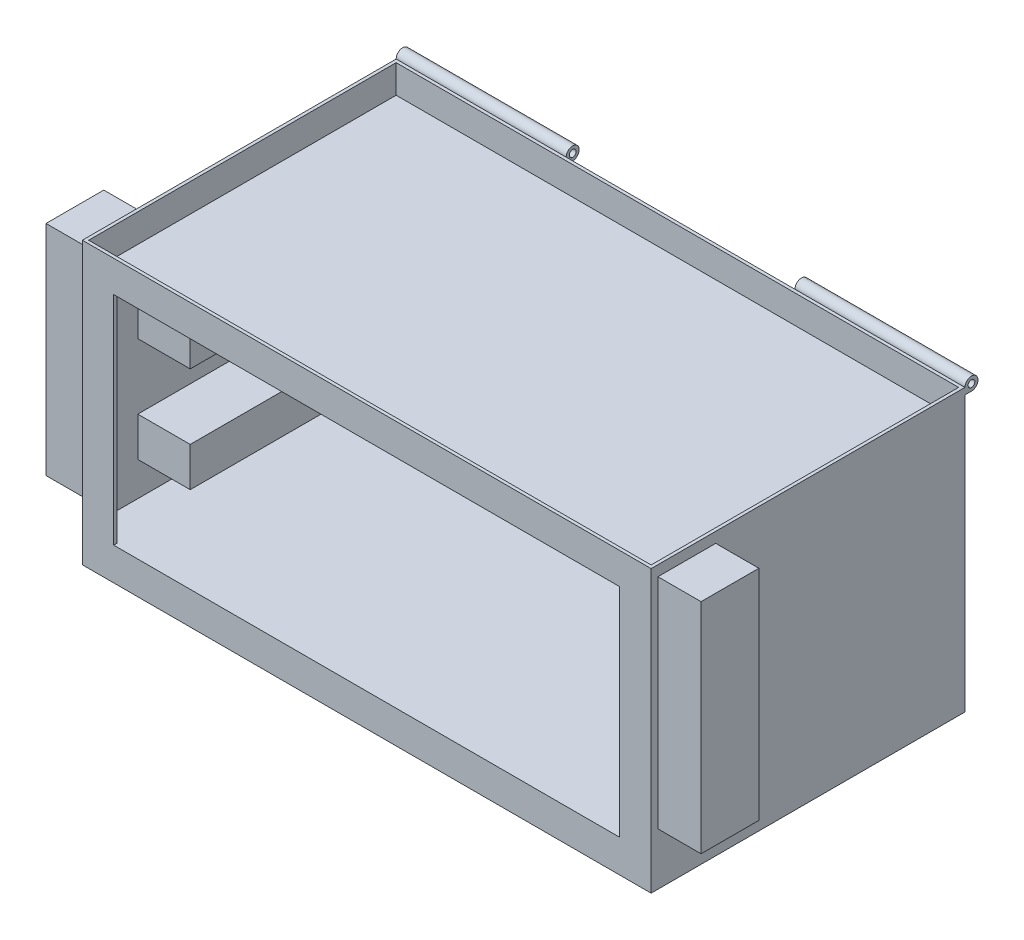
SolidWorks part; units mm, degrees
note: The reader was unsure of these and kept them because the rebuilt part matched: shared geometry of "Sketch1<13>", "Sketch1<14>", "Sketch1<15>".
material "AISI 4130 Steel, normalized at 870C"
ref_plane "Front Plane" through (0, 0, 0) normal (0, 0, 1) x (1, 0, 0)
ref_plane "Top Plane" through (0, 0, 0) normal (0, 1, 0) x (1, 0, 0)
ref_plane "Right Plane" through (0, 0, 0) normal (1, 0, 0) x (0, 0, -1)
sketch "Sketch1" plane through (0, 0, 0) normal (0, 1, 0) x (1, 0, 0)
  line L0 (0, 0) -> (-1.524, 0) construction
  line L9 (0, 0) -> (273.177, 0)
  line L10 (0, 0) -> (0, 149.352)
  line L11 (0, 149.352) -> (273.177, 149.352)
  line L12 (273.177, 0) -> (273.177, 149.352)
  line L13 (-1.524, -1.524) -> (274.701, -1.524)
  line L14 (-1.524, -1.524) -> (-1.524, 150.876)
  line L15 (-1.524, 150.876) -> (274.701, 150.876)
  line L16 (274.701, -1.524) -> (274.701, 150.876)
  line L17 (0, 149.352) -> (0, 150.876) construction
  line L18 (273.177, 149.352) -> (274.701, 149.352) construction
  line L19 (273.177, 0) -> (273.177, -1.524) construction
  line L20 (13.716, 0) -> (13.716, -1.524)
  line L21 (136.5885, 150.876) -> (136.5885, -1.524) construction
  line L22 (259.461, 0) -> (259.461, -1.524)
  dimension "D1" = 1.524
  dimension "D2" = 276.225
  dimension "D3" = 152.4
  dimension "D4" = 15.24
extrude "Bulk-Extrude" add sketch "Sketch1" against normal blind 136.525 contours L14 L13 L16 L15
extrude "Inner Shell-Cut" cut sketch "Sketch1<13>" against normal offset from surface (120.65 mm away) 15.875 contours L9 L12 L11 L10 | L22 L9 L20 L13 up to face at (136.5885, -136.525, -74.676)
sketch "Sketch1<13>" plane through (0, 0, 0) normal (0, 1, 0) x (1, 0, 0) same geometry as "Sketch1"
extrude "Top Wall-Extrude" add sketch "Sketch1<14>" against normal blind 15.24 contours L22 L9 L20 L13
sketch "Sketch1<14>" plane through (0, 0, 0) normal (0, 1, 0) x (1, 0, 0) same geometry as "Sketch1"
extrude "Top Floor-Extrude" add sketch "Sketch1<15>" along normal blind 1.524 from surface at -15.24 contours L9 L12 L11 L10 starting at face at (136.5885, -15.24, 0.762)
sketch "Sketch1<15>" plane through (0, 0, 0) normal (0, 1, 0) x (1, 0, 0) same geometry as "Sketch1"
ref_plane "Mid Plane" through (136.5885, 0, 0) normal (1, 0, 0) x (0, 0, -1)
sketch "Sketch5" plane through (274.701, 0, 0) normal (1, 0, 0) x (0, 0, -1)
  line L0 (150.876, 0) -> (154.051, 0)
  line L2 (154.051, -3.175) -> (150.876, -3.175)
  line L3 (150.876, -136.525) -> (150.876, 0) construction
  circle A0 centre (154.051, 0) radius 3.175
  circle A1 centre (154.051, 0) radius 1.651
  dimension "D1" = 1.524
  dimension "D2" = 6.35
extrude "Hinge-Extrude" add sketch "Sketch5" against normal blind 82.55
mirror "Mirror1" about plane through (136.5885, 0, 0) normal (1, 0, 0) of "Hinge-Extrude"
sketch "Sketch7" plane through (0, 0, -149.352) normal (0, 0, 1) x (1, 0, 0)
  line L0 (273.177, -120.65) -> (273.177, -15.24) construction
  line L1 (0, -34.29) -> (25.4635, -34.29)
  line L2 (0, -34.29) -> (0, -53.34)
  line L3 (0, -53.34) -> (25.4635, -53.34)
  line L4 (25.4635, -34.29) -> (25.4635, -53.34)
  line L5 (273.177, -34.29) -> (247.7135, -34.29)
  line L6 (273.177, -34.29) -> (273.177, -53.34)
  line L7 (273.177, -53.34) -> (247.7135, -53.34)
  line L8 (247.7135, -34.29) -> (247.7135, -53.34)
  line L9 (0, -120.65) -> (0, -15.24) construction
  line L10 (0, -85.09) -> (25.4635, -85.09)
  line L11 (0, -85.09) -> (0, -104.14)
  line L12 (0, -104.14) -> (25.4635, -104.14)
  line L13 (25.4635, -85.09) -> (25.4635, -104.14)
  line L14 (0, -15.24) -> (0, -34.29) construction
  line L15 (273.177, -85.09) -> (247.7135, -85.09)
  line L16 (273.177, -85.09) -> (273.177, -104.14)
  line L17 (273.177, -104.14) -> (247.7135, -104.14)
  line L18 (247.7135, -85.09) -> (247.7135, -104.14)
  line L19 (0, -15.24) -> (273.177, -15.24) construction
  line L20 (273.177, -15.24) -> (273.177, -34.29) construction
  line L21 (0, -53.34) -> (0, -85.09) construction
  line L22 (273.177, -53.34) -> (273.177, -85.09) construction
  dimension "D1" = 19.05
  dimension "D2" = 31.75
  dimension "D3" = 19.05
  dimension "D4" = 222.25
extrude "Rails-Extrude" add sketch "Sketch7" along normal offset from surface (125.476 mm away) 25.4 up to face at (136.5885, -68.2625, 1.524)
sketch "Sketch8" [suppressed] plane through (274.701, 0, 0) normal (1, 0, 0) x (0, 0, -1)
  line L0 (-1.524, -129.2098) -> (150.876, -129.2098) construction
  line L1 (-1.524, -136.525) -> (-1.524, 0) construction
  line L2 (150.876, -136.525) -> (150.876, -3.175) construction
  line L3 (-1.524, -136.525) -> (150.876, -136.525) construction
  line L4 (-1.524, -121.8946) -> (150.876, -121.8946) construction
  line L5 (-1.524, -135.89) -> (150.876, -135.89) construction
  line L6 (-0.889, -121.8946) -> (-0.889, -136.525) construction
  line L7 (150.241, -121.8946) -> (150.241, -136.525) construction
  line L8 (74.676, -135.89) -> (74.676, 0) construction
  line L9 (-1.524, 0) -> (150.876, 0) construction
  circle A0 centre (11.176, -129.2098) radius 4.7625
  circle A1 centre (138.176, -129.2098) radius 4.7625
  dimension "D6" = 9.525
  dimension "D7" = 12.7
  dimension "D1" = 7.3152
  dimension "D2" = 14.6304
  dimension "D3" = 0.635
  dimension "D4" = 0.635
  dimension "D5" = 0.635
sketch "Sketch9" plane through (274.701, 0, 0) normal (1, 0, 0) x (0, 0, -1)
  line L0 (-1.524, -136.525) -> (-1.524, 0) construction
  line L1 (1.778, -111.125) -> (29.845, -111.125)
  line L2 (1.778, -111.125) -> (1.778, -5.08)
  line L3 (1.778, -5.08) -> (29.845, -5.08)
  line L4 (29.845, -111.125) -> (29.845, -5.08)
  line L5 (-1.524, -136.525) -> (150.876, -136.525) construction
  line L6 (-1.524, 0) -> (150.876, 0) construction
  dimension "D1" = 28.067
  dimension "D2" = 3.302
  dimension "D3" = 25.4
  dimension "D4" = 5.08
extrude "Latch Clear. Box, Right-Extrude" add sketch "Sketch9" along normal blind 20.955 separate body contours L2 L1 L4 L3
mirror "Latch Clear. Box, Left-Mirror" about plane through (136.5885, 0, 0) normal (1, 0, 0) of "Latch Clear. Box, Right-Extrude"
